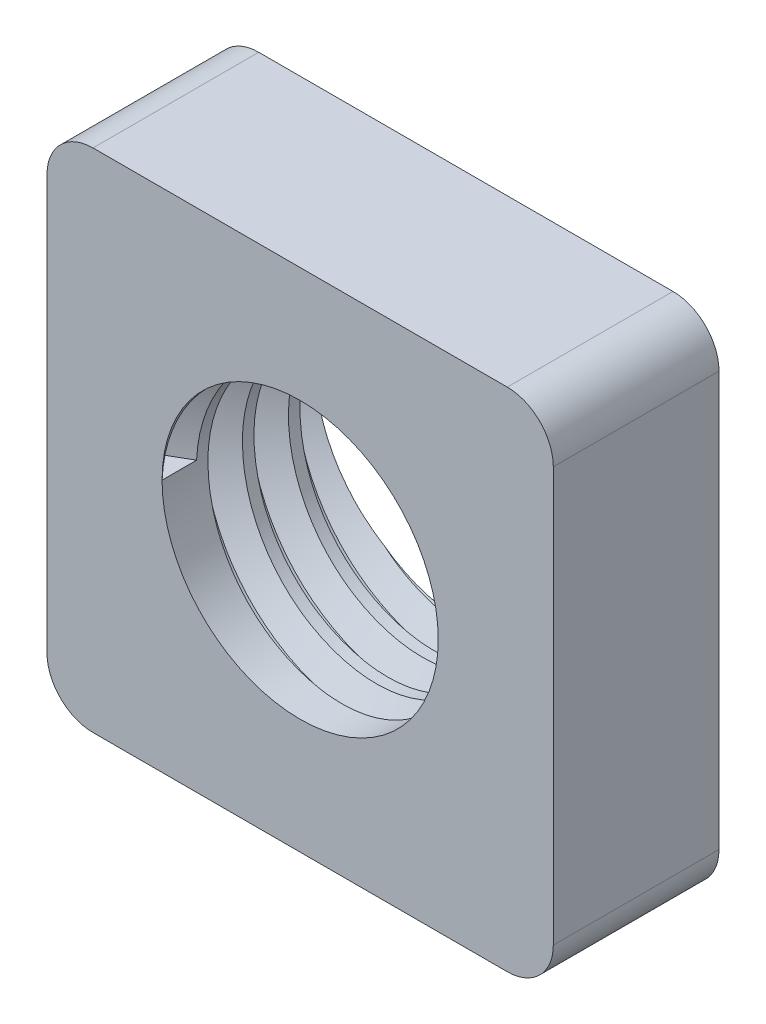
SolidWorks part; units mm, degrees
material "Plain Carbon Steel"
ref_plane "Front Plane" through (0, 0, 0) normal (0, 0, 1) x (1, 0, 0)
ref_plane "Top Plane" through (0, 0, 0) normal (0, 1, 0) x (1, 0, 0)
ref_plane "Right Plane" through (0, 0, 0) normal (1, 0, 0) x (0, 0, -1)
sketch "Sketch1" plane through (0, 0, 0) normal (0, 0, 1) x (1, 0, 0)
  line L1 (2.75, -2.75) -> (-2.75, -2.75)
  line L2 (2.75, -2.75) -> (2.75, 2.75)
  line L3 (2.75, 2.75) -> (-2.75, 2.75)
  line L4 (-2.75, -2.75) -> (-2.75, 2.75)
  line L5 (2.75, -2.75) -> (-2.75, 2.75) construction
  line L6 (2.75, 2.75) -> (-2.75, -2.75) construction
  circle A0 centre (0, 0) radius 1.5
  point P0 (0, 0)
  dimension "D3" = 3
  dimension "D1" = 5.5
  dimension "D2" = 5.5
extrude "Boss-Extrude1" add sketch "Sketch1" along normal blind 1.8
fillet "Fillet1" radius 0.5 4 edges at (2.75, -2.75, 0.9) (-2.75, -2.75, 0.9) (-2.75, 2.75, 0.9) (2.75, 2.75, 0.9)
thread "Thread1" pitch 0.5 method cut profile "Thread Profile1" start angle 0, offset 0, length 10, pitch 0.5, diameter 3
ref_plane "Plane1" through (-1.5, 0, 1.8) normal (0, -1, 0) x (-1, 0, 0)
sketch "Thread Profile1" plane through (-1.5, 0, 1.8) normal (0, -1, 0) x (-1, 0, 0)
  line L0 (0, 0) -> (0, 0.5) construction
  line L1 (0, 0) -> (0.2706, 0.1562)
  line L2 (0.2706, 0.1562) -> (0.2706, 0.2187)
  line L3 (0.2706, 0.2187) -> (0, 0.375)
  line L4 (0.2706, 0.1875) -> (0, 0.1875) construction
  line L11 (0, 0) -> (0, 0.375)
  point P2 (0, 0)
  dimension "Pitch" = 0.5
  dimension "Profile_Angle" = 60
  dimension "Profile_Land" = 0.0625
  dimension "Profile_Height" = 0.2706
